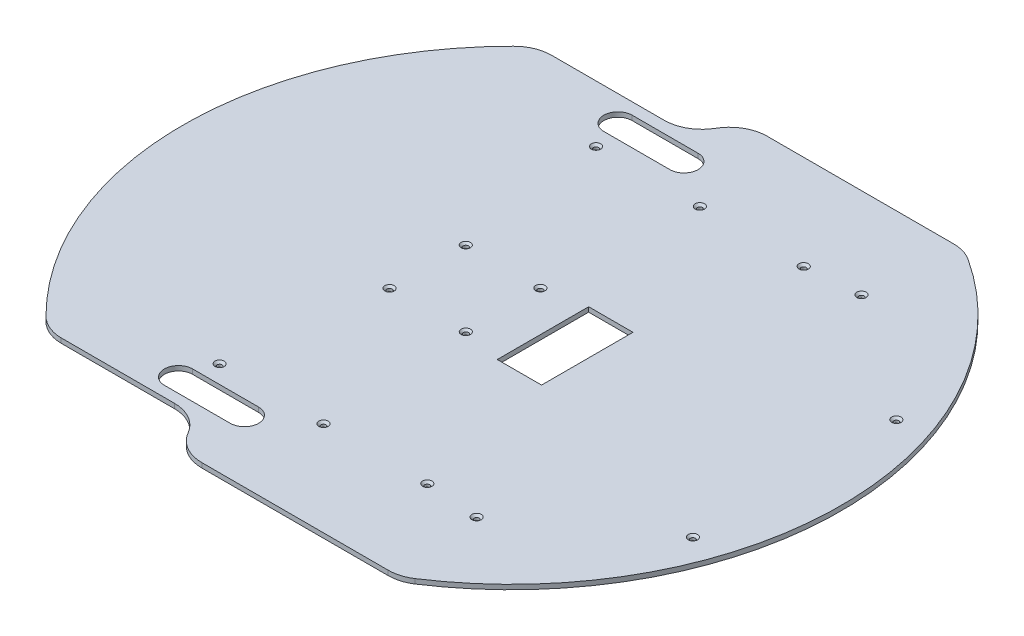
SolidWorks part; units mm, degrees
ref_plane "Plan de face" through (0, 0, 0) normal (0, 0, 1) x (1, 0, 0)
ref_plane "Plan de dessus" through (0, 0, 0) normal (0, 1, 0) x (1, 0, 0)
ref_plane "Plan de droite" through (0, 0, 0) normal (1, 0, 0) x (0, 0, -1)
sketch "Esquisse1" plane through (0, 0, 0) normal (0, 1, 0) x (1, 0, 0)
  line L0 (-138.94, 165.455) -> (-62.65, 165.455)
  line L5 (106.95, -190.145) -> (-18.65, -190.145)
  line L7 (-18.65, 190.855) -> (106.95, 190.855)
  line L8 (-138.94, -164.745) -> (-62.65, -164.745)
  arc A1 (-156.83, 157.725) -> (-138.94, 165.455) centre (-138.5811, 140.0575) cw
  arc A2 (-62.65, 165.455) -> (-40.65, 178.155) centre (-62.647, 190.855) ccw
  arc A3 (-40.65, 178.155) -> (-18.65, 190.855) centre (-18.653, 165.455) cw
  arc A4 (106.95, 190.855) -> (120.78, 186.755) centre (106.9427, 165.455) cw
  arc A5 (120.78, 186.755) -> (120.78, -186.045) centre (-0.716, 0.355) cw
  arc A6 (120.78, -186.045) -> (106.95, -190.145) centre (106.9427, -164.745) cw
  arc A7 (-18.65, -190.145) -> (-40.65, -177.445) centre (-18.653, -164.745) cw
  arc A8 (-40.65, -177.445) -> (-62.65, -164.745) centre (-62.647, -190.145) ccw
  arc A9 (-156.83, -157.015) -> (-138.94, -164.745) centre (-138.5811, -139.3475) ccw
  arc A10 (-156.83, 157.725) -> (-156.83, -157.015) centre (0.4625, 0.355) ccw
  point P0 (0, 0)
  dimension "D3" = 222.5
  dimension "D5" = 25.4
  dimension "D7" = 25.4
  dimension "D9" = 25.4
  dimension "D12" = 25.4
  dimension "D14" = 222.5
  dimension "D15" = 25.4
  dimension "D18" = 25.4
  dimension "D19" = 76.29
  dimension "D21" = 25.4
  dimension "D22" = 25.4
  dimension "D2" = 125.6
  dimension "D4" = 157.725
  dimension "D6" = 76.29
  dimension "D8" = 22
  dimension "D10" = 22
  dimension "D11" = 125.6
  dimension "D13" = 4.1
  dimension "D16" = 4.1
  dimension "D17" = 13.83
  dimension "D20" = 22
  dimension "D23" = 381
  dimension "D24" = 277.61
  dimension "D25" = 330.2
  dimension "D26" = 22
  dimension "D27" = 17.89
  dimension "D28" = 17.89
  dimension "D29" = 7.73
  dimension "D30" = 7.73
  dimension "D31" = 25.4
  dimension "D32" = 156.83
extrude "Boss.-Extru.1" add sketch "Esquisse1" along normal blind 3.18
sketch "Esquisse2" plane through (0, 3.18, 0) normal (0, 1, 0) x (1, 0, 0)
  line L0 (-76.45, -148.105) -> (-32, -148.105) construction
  line L1 (-76.45, -138.575) -> (-32, -138.575)
  line L2 (-76.45, -157.635) -> (-32, -157.635)
  line L3 (-138.94, -164.745) -> (-62.65, -164.745) construction
  line L4 (0, 0) -> (-294.8551, 0) construction
  line L5 (-76.45, 148.105) -> (-32, 148.105) construction
  line L6 (-76.45, 138.575) -> (-32, 138.575)
  line L7 (-76.45, 157.635) -> (-32, 157.635)
  line L8 (20.7, -30.425) -> (50.55, -30.425)
  line L9 (20.7, -30.425) -> (20.7, 31.175)
  line L10 (20.7, 31.175) -> (50.55, 31.175)
  line L11 (50.55, -30.425) -> (50.55, 31.175)
  arc A0 (-76.45, -138.575) -> (-76.45, -157.635) centre (-76.45, -148.105) ccw
  arc A1 (-32, -157.635) -> (-32, -138.575) centre (-32, -148.105) ccw
  arc A2 (-76.45, 138.575) -> (-76.45, 157.635) centre (-76.45, 148.105) cw
  arc A3 (-32, 157.635) -> (-32, 138.575) centre (-32, 148.105) cw
  point P2 (-54.225, -148.105)
  point P15 (-54.225, 148.105)
  dimension "D1" = 9.53
  dimension "D2" = 7.11
  dimension "D3" = 13.8
  dimension "D4" = 44.45
  dimension "D5" = 61.6
  dimension "D6" = 159.64
  dimension "D7" = 134.32
  dimension "D8" = 29.85
extrude "Enlèv. mat.-Extru.1" cut sketch "Esquisse2" against normal blind 3.18
sketch "Esquisse3" plane through (0, 3.18, 0) normal (0, 1, 0) x (1, 0, 0)
  line L1 (0.4625, 0.355) -> (-274.8168, 0.355) construction
  point P0 (-70.35, -126.475)
  point P1 (-0.37, -126.475)
  point P3 (69.61, -126.475)
  point P5 (105.7, -129.345)
  point P8 (190.32, -68.205)
  point P10 (190.32, 68.915)
  point P11 (105.7, 130.055)
  point P12 (69.61, 127.185)
  point P13 (-0.37, 127.185)
  point P14 (-70.35, 127.185)
  dimension "D1" = 12.1
  dimension "D2" = 6.1
  dimension "D3" = 69.98
  dimension "D4" = 69.98
  dimension "D5" = 2.87
  dimension "D6" = 36.09
  dimension "D7" = 84.62
  dimension "D8" = 61.14
hole_wizard "Fraisage pour vis à tête fraisée M31" positions "Esquisse3D2" profile "Esquisse8" countersink size "M3" standard "Ansi Metric" end condition through all
sketch3d "Esquisse3D2"
  point P0 (-70.35, 3.18, 126.475)
  point P3 (-0.37, 3.18, 126.475)
  point P6 (69.61, 3.18, 126.475)
  point P9 (105.7, 3.18, 129.345)
  point P12 (190.32, 3.18, 68.205)
  point P15 (190.32, 3.18, -68.915)
  point P18 (105.7, 3.18, -130.055)
  point P21 (69.61, 3.18, -127.185)
  point P24 (-0.37, 3.18, -127.185)
  point P27 (-70.35, 3.18, -127.185)
sketch "Esquisse8" plane through (-70.35, 3.18, 126.475) normal (1, 0, 0) x (0, 0, 1)
  line L0 (0, 0) -> (0, 3.18)
  line L1 (0, 3.18) -> (1.7, 3.18)
  line L2 (1.7, 3.18) -> (1.7, 1.45)
  line L3 (1.7, 1.45) -> (3.15, 0)
  line L5 (3.15, 0) -> (0, 0)
  line L6 (-1.7, 1.45) -> (-3.15, 0) construction
  line L11 (0, -6.35) -> (0, 107.95) construction
  dimension "Diamètre du perçage jusqu'au prochain" = 3.4
  dimension "Profondeur du perçage jusqu'au prochain" = 3.18
  dimension "Diamètre du fraisage entrant" = 6.3
  dimension "Angle du fraisage entrant" = 90
sketch "Esquisse9" plane through (0, 3.18, 0) normal (0, 1, 0) x (1, 0, 0)
  line L0 (20.7, 31.175) -> (20.7, -30.425) construction
  line L1 (-151.0308, 0.355) -> (43.8249, -112.145) construction
  line L2 (43.8249, -112.145) -> (43.8249, 112.855) construction
  line L3 (43.8249, 112.855) -> (-151.0308, 0.355) construction
  line L13 (-4.72, 27.445) -> (-4.72, -26.555) construction
  line L14 (-4.72, -26.555) -> (-59.23, -26.5244) construction
  line L15 (-59.23, -26.5244) -> (-58.3786, 27.829) construction
  line L16 (-58.3786, 27.829) -> (-4.72, 27.445) construction
  line L17 (0.4625, 0.355) -> (-274.8168, 0.355) construction
  circle A0 centre (-21.127, 0.355) radius 64.9519 construction
  point P8 (0, 0)
  point P15 (-14.53, 0)
  dimension "D2" = 54.36
  dimension "D1" = 225
  dimension "D3" = 54
  dimension "D4" = 3.73
  dimension "D5" = 25.42
  dimension "D6" = 53.66
  dimension "D7" = 54.51
  dimension "D8" = 90.41
  dimension "D9" = 90.487
  dimension "D10" = 21.13
  dimension "D11" = 0
sketch "Esquisse11" plane through (0, 3.18, 0) normal (0, 1, 0) x (1, 0, 0)
  line L0 (-56.6966, 25.755) -> (-6.0543, -24.8462) construction
  line L1 (-58.3873, 27.46) -> (-4.7273, 27.46) construction
  line L2 (-58.3873, 27.46) -> (-58.8471, -26.8981) construction
  line L3 (-58.8471, -26.8981) -> (-4.3371, -26.54) construction
  line L4 (-4.7273, 27.46) -> (-4.3371, -26.54) construction
  circle A0 centre (-56.6966, 25.755) radius 1.705 construction
  circle A1 centre (-6.0543, -24.8462) radius 1.705 construction
  circle A2 centre (-57.1275, -25.1817) radius 1.705 construction
  circle A3 centre (-6.42, 25.755) radius 1.705 construction
  dimension "D5" = 3.41
  dimension "D6" = 54.51
  dimension "D1" = 54.36
  dimension "D2" = 71.59
  dimension "D3" = 53.66
  dimension "D4" = 54
  dimension "D7" = 27.12
  dimension "D8" = 5.42
hole_wizard "Fraisage pour vis à tête fraisée M33" positions "Esquisse3D4" profile "Esquisse12" countersink size "M3" standard "Ansi Metric" end condition through all
sketch3d "Esquisse3D4"
  point P0 (-56.6966, 3.18, -25.755)
  point P3 (-6.42, 3.18, -25.755)
  point P6 (-6.0543, 3.18, 24.8462)
  point P9 (-57.1275, 3.18, 25.1817)
sketch "Esquisse12" plane through (-56.6966, 3.18, -25.755) normal (1, 0, 0) x (0, 0, 1)
  line L0 (0, 0) -> (0, 3.18)
  line L1 (0, 3.18) -> (1.8, 3.18)
  line L2 (1.8, 3.18) -> (1.8, 1.35)
  line L3 (1.8, 1.35) -> (3.15, 0)
  line L5 (3.15, 0) -> (0, 0)
  line L6 (-1.8, 1.35) -> (-3.15, 0) construction
  line L11 (0, -6.35) -> (0, 107.95) construction
  dimension "Diamètre du perçage jusqu'au prochain" = 3.6
  dimension "Profondeur du perçage jusqu'au prochain" = 3.18
  dimension "Diamètre du fraisage entrant" = 6.3
  dimension "Angle du fraisage entrant" = 90
sketch "Esquisse13" plane through (0, 3.18, 3.18) normal (0, 1, 0) x (1, 0, 0)
  line L70 (37.71, -113.6751) -> (63.6908, -98.6751) construction
  line L71 (-151.4475, 25.535) -> (-149.8075, 25.535) construction
  line L72 (-151.4475, 25.535) -> (-151.4475, -4.465) construction
  line L73 (-151.4475, -4.465) -> (-149.8075, -4.465) construction
  line L74 (-149.8075, 25.535) -> (-149.8075, -4.465) construction
  line L75 (44.2282, -108.965) -> (44.2282, 116.035) construction
  line L76 (44.2282, 116.035) -> (-150.6275, 3.535) construction
  line L77 (-150.6275, 3.535) -> (44.2282, -108.965) construction
  line L82 (63.6908, -98.6751) -> (62.8708, -97.2549) construction
  line L83 (62.8708, -97.2549) -> (36.89, -112.2549) construction
  line L84 (36.89, -112.2549) -> (37.71, -113.6751) construction
  line L85 (36.89, 119.3249) -> (62.8708, 104.3249) construction
  line L86 (62.8708, 104.3249) -> (63.6908, 105.7451) construction
  line L87 (63.6908, 105.7451) -> (37.71, 120.7451) construction
  line L88 (37.71, 120.7451) -> (36.89, 119.3249) construction
  line L92 (0.4625, 3.535) -> (-274.8168, 3.535) construction
  circle A4 centre (-150.6275, 3.535) radius 5 construction
  circle A5 centre (44.2282, 116.035) radius 5 construction
  circle A6 centre (44.2282, -108.965) radius 5 construction
  circle A11 centre (-20.7237, 3.535) radius 64.9519 construction
  circle A12 centre (69.61, 130.365) radius 3.15 construction
  circle A13 centre (105.7, 133.235) radius 3.15 construction
  circle A14 centre (69.61, -123.295) radius 3.15 construction
  circle A15 centre (105.7, -126.165) radius 3.15 construction
  point P1 (-26.3388, 3.535)
  point P3 (-21.127, 3.535)
  point P4 (-21.127, 3.535)
  point P25 (0, 0)
  point P26 (0, 0)
  point P27 (52.9571, -110.8887)
  point P28 (-21.127, 3.535)
  point P29 (-21.127, -22.6074)
  point P30 (-21.127, 11.2784)
  point P31 (-21.127, 6.5979)
  point P33 (-20.7288, 3.18)
  point P35 (88.2038, -113.471)
  dimension "D9" = 25.3818
  dimension "D27" = 8
  dimension "D31" = 1.64
  dimension "D32" = 0.82
  dimension "D33" = 8
  dimension "D34" = 225
  dimension "D3" = 60
  dimension "D4" = 60
  dimension "D5" = 60
  dimension "D6" = 93.5
  dimension "D7" = 25.3818
  dimension "D8" = 14.33
  dimension "D10" = 14.33
  dimension "D16" = 0
  dimension "D17" = 0
  dimension "D20" = 1.64
  dimension "D21" = 8
  dimension "D22" = 0.82
  dimension "D23" = 1.64
  dimension "D24" = 30
  dimension "D25" = 30
  dimension "D28" = 0.82
  dimension "D29" = 60
  dimension "D30" = 30
  dimension "D35" = 60
